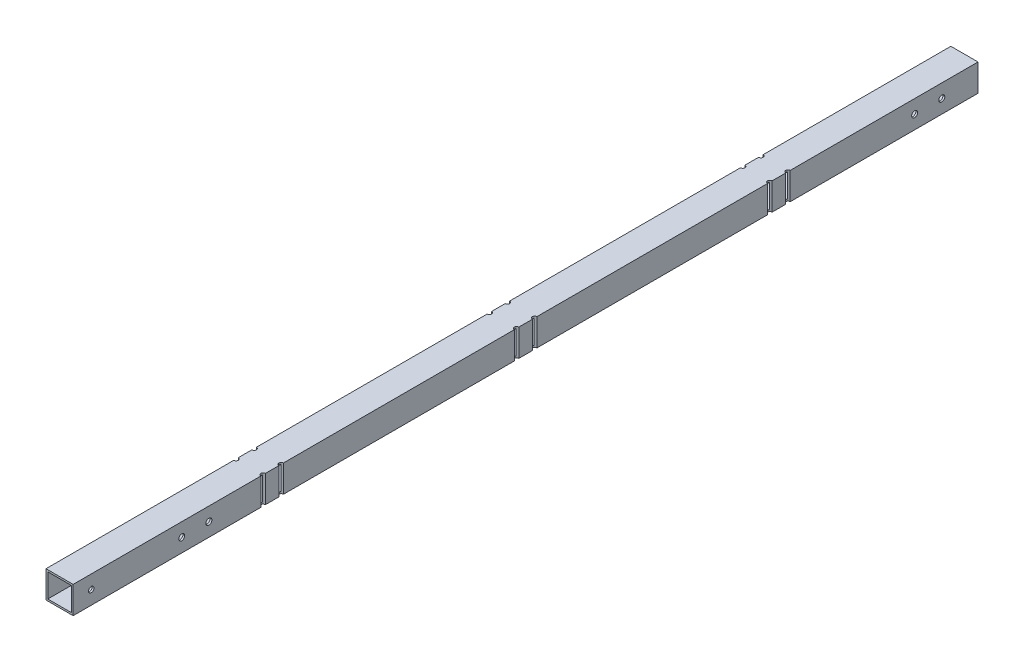
SolidWorks part; units mm, degrees
material "1060 合金"
ref_plane "前视基准面" through (0, 0, 0) normal (0, 0, 1) x (1, 0, 0)
ref_plane "上视基准面" through (0, 0, 0) normal (0, 1, 0) x (1, 0, 0)
ref_plane "右视基准面" through (0, 0, 0) normal (1, 0, 0) x (0, 0, -1)
other "Configuration Table"
sketch "草图1" plane through (0, 0, 0) normal (0, 0, 1) x (1, 0, 0)
  line L1 (0, 0) -> (15, 0)
  line L2 (0, 0) -> (0, -15)
  line L3 (0, -15) -> (15, -15)
  line L4 (15, 0) -> (15, -15)
  dimension "D1" = 15
  dimension "D2" = 15
extrude "拉伸-薄壁1" add sketch "草图1" along normal blind 800 thin thin type one direction reverse wall 1
sketch "草图2" plane through (0, -15, 0) normal (0, -1, 0) x (1, 0, 0)
  circle A1 centre (7.5, 825) radius 2.6
  circle A2 centre (7.5, 825) radius 2.6
  dimension "D1" = 0
extrude "切除-拉伸1" [suppressed] cut sketch "草图2" against normal up to next
sketch "草图3" plane through (0, 0, 0) normal (-1, 0, 0) x (0, 0, 1)
  line L0 (800, 0) -> (0, 0) construction
  line L1 (0, 0) -> (0, -15) construction
  circle A0 centre (215, -7.5) radius 1.7
  circle A1 centre (170, -7.5) radius 1.7
  dimension "D1" = 3.4
  dimension "D2" = 3.4
  dimension "D3" = 45
  dimension "D4" = 7.5
  dimension "D5" = 7.5
  dimension "D6" = 170
sketch "草图4" plane through (15, 0, 0) normal (1, 0, 0) x (0, 0, -1)
  line L0 (-800, -15) -> (0, -15) construction
  line L1 (-800, -15) -> (-800, 0) construction
  circle A0 centre (-790, -7.5) radius 1.5
  dimension "D1" = 3
  dimension "D2" = 7.5
  dimension "D3" = 10
extrude "切除-拉伸3" cut sketch "草图4" against normal through all
sketch "草图5" plane through (15, 0, 0) normal (1, 0, 0) x (0, 0, -1)
  line L0 (-800, 0) -> (0, 0) construction
  line L1 (0, -15) -> (0, 0) construction
  line L2 (-800, -1) -> (-800, -14) construction
  circle A0 centre (-320, -7.5) radius 1.65
  circle A1 centre (-335, -7.5) radius 1.65
  circle A2 centre (-725, -7.5) radius 1.65
  circle A3 centre (-740, -7.5) radius 1.65
  dimension "D1" = 3.3
  dimension "D4" = 3.3
  dimension "D7" = 7.5
  dimension "D9" = 3.3
  dimension "D10" = 3.3
  dimension "D2" = 7.5
  dimension "D3" = 15
  dimension "D5" = 7.5
  dimension "D6" = 320
  dimension "D8" = 7.5
  dimension "D11" = 15
  dimension "D12" = 60
extrude "切除-拉伸4" cut sketch "草图5" against normal through all
sketch "草图6" plane through (0, 0, 0) normal (0, 0, -1) x (-1, 0, 0)
  line L4 (0, -15) -> (0, 0)
  line L5 (0, 0) -> (-15, 0)
  line L6 (-15, 0) -> (-15, -15)
  line L7 (-15, -15) -> (0, -15)
  line L8 (0, -15) -> (0, 0)
  line L9 (0, 0) -> (-15, 0)
  line L10 (-15, 0) -> (-15, -15)
  line L11 (-15, -15) -> (0, -15)
  dimension "D1" = 0
extrude "切除-拉伸5" cut sketch "草图6" against normal blind 300
sketch "草图7" plane through (0, 0, 0) normal (0, 1, 0) x (1, 0, 0)
  line L0 (7.5, -300) -> (7.5, -861.2957) construction
  line L1 (0, -300) -> (15, -300) construction
  line L2 (0, -550) -> (263.5539, -550) construction
  line L3 (0, -800) -> (0, -300) construction
  circle A0 centre (0, -545) radius 1.25
  circle A1 centre (15, -545) radius 1.25
  circle A2 centre (15, -555) radius 1.25
  circle A3 centre (0, -555) radius 1.25
  circle A4 centre (0, -405) radius 1.25
  circle A5 centre (15, -405) radius 1.25
  circle A6 centre (15, -415) radius 1.25
  circle A7 centre (0, -415) radius 1.25
  circle A8 centre (0, -685) radius 1.25
  circle A9 centre (15, -685) radius 1.25
  circle A10 centre (15, -695) radius 1.25
  circle A11 centre (0, -695) radius 1.25
  circle A12 centre (0, -545) radius 1.25
  circle A13 centre (15, -545) radius 1.25
  circle A14 centre (15, -555) radius 1.25
  circle A15 centre (0, -555) radius 1.25
  point P36 (0, 0)
  line M12 (0, -300) -> (0, -800)
  line M14 (15, -800) -> (15, -300)
  dimension "D1" = 2.5
  dimension "D3" = 15
  dimension "D4" = 10
  dimension "D2" = 250
  dimension "D6" = 135
  dimension "D5" = 2
extrude "切除-拉伸6" cut sketch "草图7" against normal blind 155 contours A4 M12 | A7 M12 | A5 M14 | A6 M14 | A1 M14 | A0 M12 | A2 M14 | A8 M12 | A11 M12 | A9 M14 | A10 M14 | A3 region at (0.5305, 0, 545) region at (0.5305, 0, 695) region at (0.5305, 0, 685) region at (0.5305, 0, 405) region at (0.5305, 0, 415) region at (14.4695, 0, 695) region at (14.4695, 0, 685) region at (14.4695, 0, 555) region at (14.4695, 0, 405) region at (14.4695, 0, 415) region at (14.4695, 0, 545)
